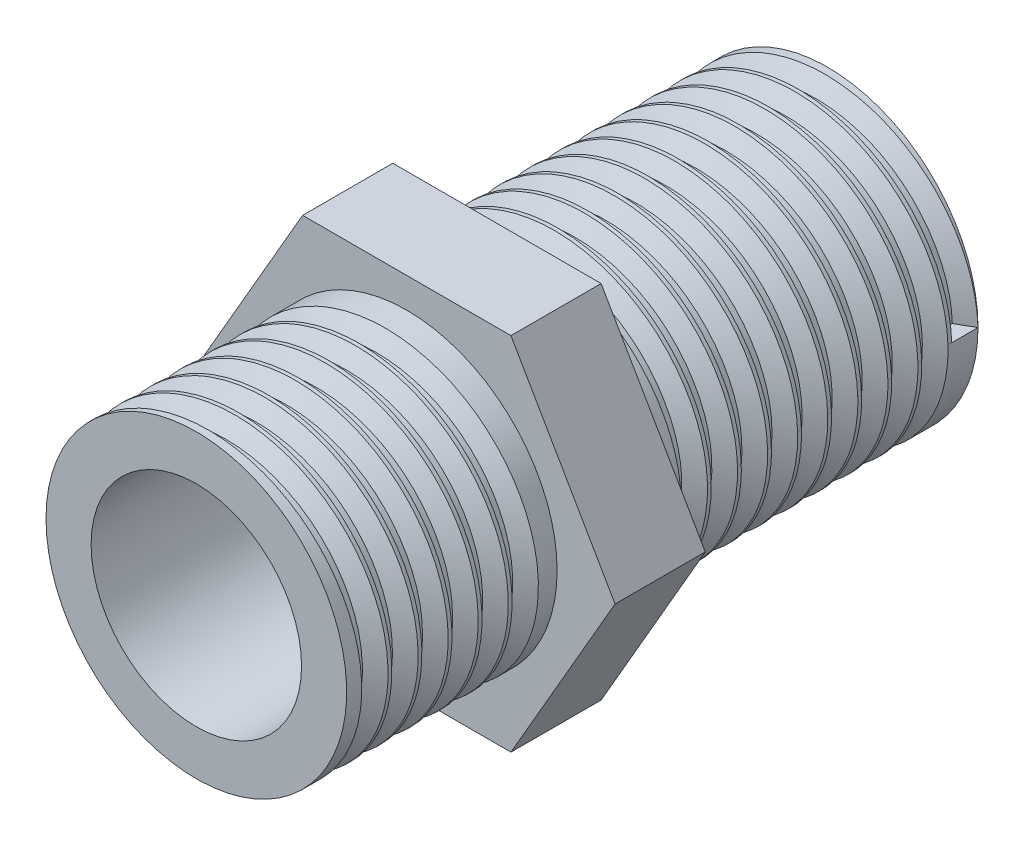
SolidWorks part; units mm, degrees
ref_plane "Front Plane" through (0, 0, 0) normal (0, 0, 1) x (1, 0, 0)
ref_plane "Top Plane" through (0, 0, 0) normal (0, 1, 0) x (1, 0, 0)
ref_plane "Right Plane" through (0, 0, 0) normal (1, 0, 0) x (0, 0, -1)
sketch "Sketch5" plane through (0, 0, 0) normal (0, 0, 1) x (1, 0, 0)
  line L1 (6.9282, 0) -> (3.4641, 6)
  line L2 (3.4641, 6) -> (-3.4641, 6)
  line L3 (-3.4641, 6) -> (-6.9282, 0)
  line L4 (-6.9282, 0) -> (-3.4641, -6)
  line L5 (-3.4641, -6) -> (3.4641, -6)
  line L6 (3.4641, -6) -> (6.9282, 0)
  circle A0 centre (0, 0) radius 6 construction
  dimension "D1" = 12
extrude "Boss-Extrude1" add sketch "Sketch5" along normal blind 3
sketch "Sketch6" plane through (0, 0, 3) normal (0, 0, 1) x (1, 0, 0)
  circle A0 centre (0, 0) radius 5
  dimension "D1" = 10
extrude "Boss-Extrude2" add sketch "Sketch6" along normal blind 7
sketch "Sketch7" plane through (0, 0, 0) normal (0, 0, -1) x (-1, 0, 0)
  circle A0 centre (0, 0) radius 5
  dimension "D1" = 10
extrude "Boss-Extrude3" add sketch "Sketch7" along normal blind 11
sketch "Sketch8" plane through (0, 0, -11) normal (0, 0, -1) x (-1, 0, 0)
  circle A0 centre (0, 0) radius 3.5
  dimension "D1" = 7
extrude "Cut-Extrude2" cut sketch "Sketch8" against normal through all
thread "Thread1" pitch 1 method cut profile "Thread Profile2" start angle 0, offset 0, length 6, pitch 1, diameter 10
ref_plane "Plane2" through (-5, 0, 10) normal (0, -1, 0) x (-1, 0, 0)
sketch "Thread Profile2" plane through (-5, 0, 10) normal (0, -1, 0) x (-1, 0, 0)
  line L0 (0, 0) -> (0, 1) construction
  line L11 (0, 0) -> (0, 0.875)
  line L12 (0, 0.875) -> (-0.5413, 0.5625)
  line L13 (-0.5413, 0.5625) -> (-0.5413, 0.3125)
  line L15 (-0.5413, 0.3125) -> (0, 0)
  line L17 (-0.5413, 0.4375) -> (0, 0.4375) construction
  point P2 (0, 0)
  dimension "Pitch" = 1
  dimension "Profile_Angle" = 60
  dimension "Profile_Land" = 0.25
  dimension "Profile_Height" = 0.5413
thread "Thread2" pitch 1 method cut profile "Thread Profile3" start angle 0, offset 0, length 10, pitch 1, diameter 10
ref_plane "Plane3" through (5, 0, -11) normal (0, -1, 0) x (1, 0, 0)
sketch "Thread Profile3" plane through (5, 0, -11) normal (0, -1, 0) x (1, 0, 0)
  line L0 (0, 0) -> (0, 1) construction
  line L11 (0, 0) -> (0, 0.875)
  line L12 (0, 0.875) -> (-0.5413, 0.5625)
  line L13 (-0.5413, 0.5625) -> (-0.5413, 0.3125)
  line L15 (-0.5413, 0.3125) -> (0, 0)
  line L17 (-0.5413, 0.4375) -> (0, 0.4375) construction
  point P2 (0, 0)
  dimension "Pitch" = 1
  dimension "Profile_Angle" = 60
  dimension "Profile_Land" = 0.25
  dimension "Profile_Height" = 0.5413
